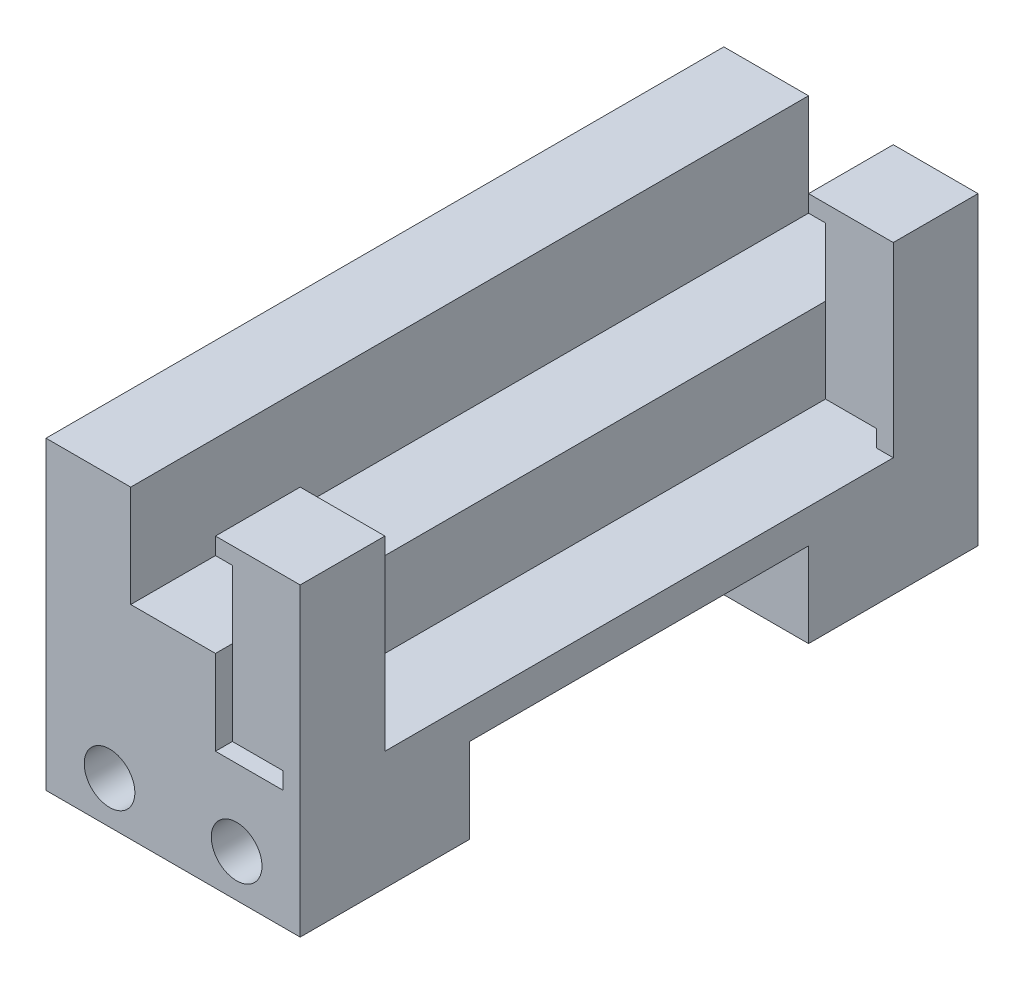
SolidWorks part; units mm, degrees
material "6061 Alloy"
ref_plane "Front Plane" through (0, 0, 0) normal (0, 0, 1) x (1, 0, 0)
ref_plane "Top Plane" through (0, 0, 0) normal (0, 1, 0) x (1, 0, 0)
ref_plane "Right Plane" through (0, 0, 0) normal (1, 0, 0) x (0, 0, -1)
sketch "Sketch2" plane through (0, 0, 0) normal (0, 0, 1) x (1, 0, 0)
  line L1 (-9.525, -9.525) -> (9.525, -9.525)
  line L2 (-9.525, -9.525) -> (-9.525, 9.525)
  line L3 (-9.525, 9.525) -> (9.525, 9.525)
  line L4 (9.525, -9.525) -> (9.525, 9.525)
  line L5 (-9.525, -9.525) -> (9.525, 9.525) construction
  line L6 (-9.525, 9.525) -> (9.525, -9.525) construction
  point P0 (0, 0)
  dimension "D1" = 19.05
  dimension "D2" = 19.05
extrude "Boss-Extrude1" add sketch "Sketch2" along normal mid plane 50.8
sketch "Sketch4" plane through (-1.5069, 3.1105, 25.4) normal (0, 0, 1) x (1, 0, 0)
  line L1 (-1.6681, 6.4145) -> (4.6819, 6.4145)
  line L2 (-1.6681, 6.4145) -> (-1.6681, -3.7455)
  line L3 (-1.6681, -3.7455) -> (4.6819, -3.7455)
  line L4 (4.6819, 6.4145) -> (4.6819, -3.7455)
  line L7 (-8.0181, 6.4145) -> (11.0319, 6.4145)
  line L8 (-8.0181, 6.4145) -> (-8.0181, 3.8745)
  line L9 (-8.0181, 3.8745) -> (11.0319, 3.8745)
  line L10 (11.0319, 6.4145) -> (11.0319, 3.8745)
  line L11 (11.0319, 6.4145) -> (-8.0181, 6.4145) construction
  line L12 (11.0319, -12.6355) -> (11.0319, 6.4145) construction
  line L13 (-8.0181, 6.4145) -> (-8.0181, -12.6355) construction
  dimension "D1" = 6.35
  dimension "D2" = 0
  dimension "D3" = 10.16
  dimension "D4" = 2.54
  dimension "D5" = 0
  dimension "D6" = 0
  dimension "D7" = 0
  dimension "D8" = 6.35
extrude "Cut-Extrude1" cut sketch "Sketch4" against normal through all contours L4 L9 | L2 L9 L4 | L9 L2 L3 L4 | L9 L2 region at (0, 8.255, 25.4) region at (-6.35, 8.255, 25.4) region at (6.35, 8.255, 25.4) region at (0, 3.175, 25.4)
sketch "Sketch6" plane through (-1.5069, 3.1105, 25.4) normal (0, 0, 1) x (1, 0, 0)
  line L0 (4.6819, 3.8745) -> (4.6819, -3.7455) construction
  line L5 (4.6819, 2.6045) -> (5.9519, 2.6045)
  line L6 (4.6819, 2.6045) -> (4.6819, -10.0955)
  line L7 (4.6819, -10.0955) -> (5.9519, -10.0955)
  line L8 (5.9519, 2.6045) -> (5.9519, -10.0955)
  line L12 (4.6819, -10.0955) -> (9.7619, -10.0955)
  line L13 (4.6819, -10.0955) -> (4.6819, -8.8255)
  line L14 (4.6819, -8.8255) -> (9.7619, -8.8255)
  line L15 (9.7619, -10.0955) -> (9.7619, -8.8255)
  line L16 (4.6819, 3.8745) -> (11.0319, 3.8745) construction
  line L17 (-8.0181, -12.6355) -> (11.0319, -12.6355) construction
  line L18 (11.0319, -12.6355) -> (11.0319, 3.8745) construction
  point P7 (5.3169, -10.0955)
  dimension "D1" = 1.27
  dimension "D2" = 1.27
  dimension "D3" = 2.54
  dimension "D4" = 1.27
  dimension "D5" = 1.27
extrude "Cut-Extrude2" cut sketch "Sketch6" against normal through all contours L6 L14 L8 L5 | L14 L6 L7 L8 | L12 L15 L14 L8 region at (3.81, 0, 25.4) region at (3.81, -6.35, 25.4) region at (6.35, -6.35, 25.4)
sketch "Sketch7" plane through (9.525, 0, 0) normal (1, 0, 0) x (0, 0, -1)
  line L0 (25.4, 6.985) -> (-25.4, 6.985) construction
  line L1 (-19.05, 6.985) -> (19.05, 6.985)
  line L2 (-19.05, 6.985) -> (-19.05, -6.985)
  line L3 (-19.05, -6.985) -> (19.05, -6.985)
  line L4 (19.05, 6.985) -> (19.05, -6.985)
  line L5 (-25.4, -9.525) -> (-25.4, 6.985) construction
  line L6 (25.4, -9.525) -> (25.4, 6.985) construction
  line L7 (-25.4, -9.525) -> (25.4, -9.525) construction
  dimension "D1" = 6.35
  dimension "D2" = 6.35
  dimension "D3" = 2.54
extrude "Cut-Extrude3" cut sketch "Sketch7" against normal up to surface (6.35 mm away) up to face at (3.175, 6.35, 0)
sketch "Sketch8" plane through (0, 0, 25.4) normal (0, 0, 1) x (1, 0, 0)
  line L0 (-9.525, -9.525) -> (9.525, -9.525)
  line L1 (-9.525, -9.525) -> (-9.525, -15.875)
  line L2 (9.525, -9.525) -> (9.525, -15.875)
  line L3 (-9.525, -15.875) -> (9.525, -15.875)
  dimension "D1" = 6.35
extrude "Boss-Extrude2" add sketch "Sketch8" against normal blind 12.7
mirror "Mirror1" about plane through (0, 0, 0) normal (0, 0, 1) of "Boss-Extrude2"
sketch "Sketch17" plane through (0, 0, 25.4) normal (0, 0, 1) x (1, 0, 0)
  line L0 (-9.525, -15.875) -> (9.525, -15.875) construction
  line L1 (-9.525, 6.985) -> (-9.525, -15.875) construction
  line L2 (9.525, -15.875) -> (9.525, 6.985) construction
  circle A0 centre (-4.7625, -12.7) radius 1.8987
  circle A1 centre (4.7625, -12.7) radius 1.8987
  dimension "D1" = 3.7973
  dimension "D2" = 3.7973
  dimension "D3" = 3.175
  dimension "D4" = 4.7625
  dimension "D5" = 3.175
  dimension "D6" = 4.7625
extrude "Cut-Extrude4" cut sketch "Sketch17" against normal up to next
